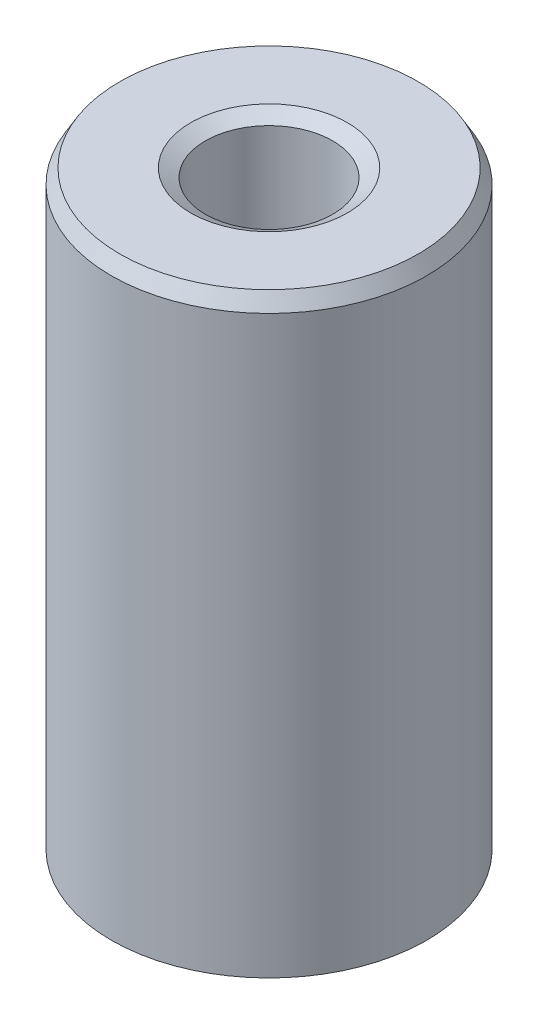
SolidWorks part; units mm, degrees
ref_plane "Front Plane" through (0, 0, 0) normal (0, 0, 1) x (1, 0, 0)
ref_plane "Top Plane" through (0, 0, 0) normal (0, 1, 0) x (1, 0, 0)
ref_plane "Right Plane" through (0, 0, 0) normal (1, 0, 0) x (0, 0, -1)
sketch "Sketch1" plane through (0, 0, 0) normal (0, 1, 0) x (1, 0, 0)
  circle A0 centre (0, 0) radius 35
  dimension "SLEEVE_OD" = 70
extrude "Boss-Extrude1" add sketch "Sketch1" along normal blind 132.8299
sketch "Sketch2" plane through (0, 0, 0) normal (0, 1, 0) x (1, 0, 0)
  circle A0 centre (0, 0) radius 14.1309
  dimension "BORE_D" = 28.2617
extrude "Cut-Extrude1" cut sketch "Sketch2" along normal through all
chamfer "Chamfer1" distance 3.2464 angle 30 4 edges at (0, 132.8299, 14.1309) (0, 0, 14.1309) (0, 0, 35) (0, 132.8299, 35) first distance on face at (0, 132.8299, 14.1309) first distance on face at (0, 0, 14.1309) first distance on face at (0, 132.8299, 35)
